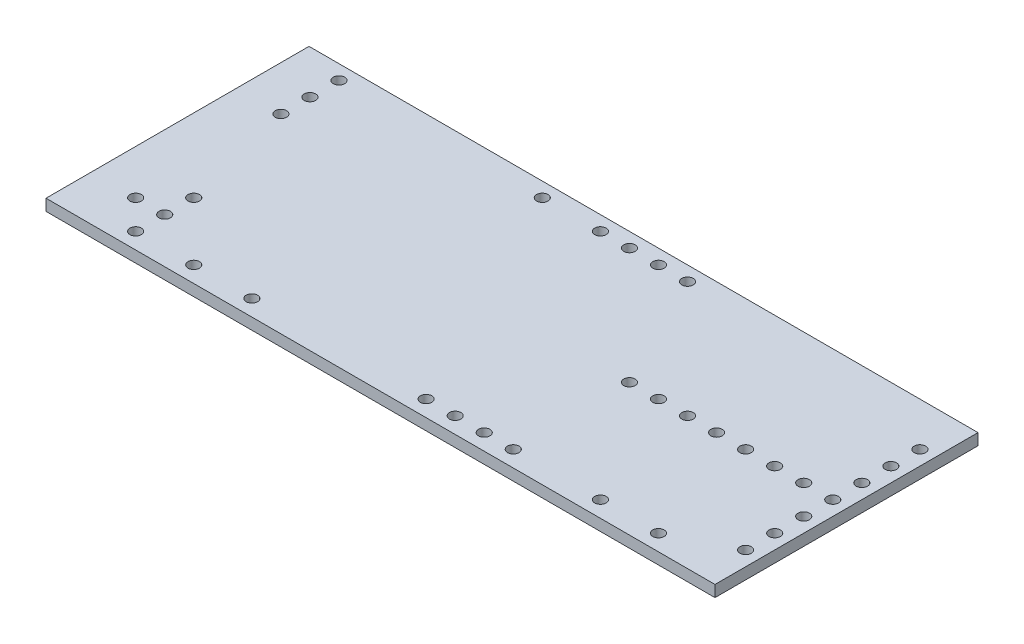
SolidWorks part; units mm, degrees
ref_plane "Front Plane" through (0, 0, 0) normal (0, 0, 1) x (1, 0, 0)
ref_plane "Top Plane" through (0, 0, 0) normal (0, 1, 0) x (1, 0, 0)
ref_plane "Right Plane" through (0, 0, 0) normal (1, 0, 0) x (0, 0, -1)
sketch "Sketch1" plane through (0, 0, 0) normal (0, 1, 0) x (1, 0, 0)
  line L1 (0, 0) -> (58.5, 0)
  line L2 (0, 0) -> (0, -23)
  line L3 (0, -23) -> (58.5, -23)
  line L4 (58.5, 0) -> (58.5, -23)
  dimension "D1" = 58.5
  dimension "D2" = 23
extrude "Boss-Extrude1" add sketch "Sketch1" along normal blind 1
sketch "Sketch2" plane through (0, 1, 0) normal (0, 1, 0) x (1, 0, 0)
  line L0 (58.5, -23) -> (58.5, 0) construction
  line L1 (58.5, 0) -> (0, 0) construction
  circle A0 centre (57.23, -3.81) radius 0.5
  circle A1 centre (57.23, -6.35) radius 0.5
  circle A2 centre (57.23, -8.89) radius 0.5
  circle A3 centre (57.23, -11.43) radius 0.5
  circle A4 centre (57.23, -13.97) radius 0.5
  circle A5 centre (57.23, -16.51) radius 0.5
  circle A6 centre (57.23, -19.05) radius 0.5
  circle A7 centre (54.69, -11.43) radius 0.5
  circle A8 centre (52.15, -11.43) radius 0.5
  circle A9 centre (49.61, -11.43) radius 0.5
  circle A10 centre (47.07, -11.43) radius 0.5
  circle A11 centre (44.53, -11.43) radius 0.5
  circle A12 centre (41.99, -11.43) radius 0.5
  circle A13 centre (39.45, -11.43) radius 0.5
  circle A14 centre (39.45, -13.97) radius 0.5 [skipped]
  circle A15 centre (39.45, -16.51) radius 0.5 [skipped]
  circle A16 centre (39.45, -19.05) radius 0.5 [skipped]
  circle A17 centre (39.45, -21.59) radius 0.5
  circle A18 centre (36.91, -21.59) radius 0.5
  circle A19 centre (34.37, -21.59) radius 0.5
  circle A20 centre (31.83, -21.59) radius 0.5
  circle A21 centre (29.29, -21.59) radius 0.5 [skipped]
  circle A22 centre (26.75, -21.59) radius 0.5 [skipped]
  circle A23 centre (24.21, -21.59) radius 0.5 [skipped]
  circle A24 centre (21.67, -21.59) radius 0.5 [skipped]
  circle A25 centre (19.13, -21.59) radius 0.5 [skipped]
  circle A26 centre (16.59, -21.59) radius 0.5
  circle A27 centre (14.05, -21.59) radius 0.5 [skipped]
  circle A28 centre (11.51, -21.59) radius 0.5
  circle A29 centre (8.97, -21.59) radius 0.5 [skipped]
  circle A30 centre (6.43, -21.59) radius 0.5
  circle A31 centre (41.99, -21.59) radius 0.5 [skipped]
  circle A32 centre (44.53, -21.59) radius 0.5 [skipped]
  circle A33 centre (47.07, -21.59) radius 0.5
  circle A34 centre (49.61, -21.59) radius 0.5 [skipped]
  circle A35 centre (52.15, -21.59) radius 0.5
  circle A36 centre (6.43, -19.05) radius 0.5
  circle A37 centre (6.43, -16.51) radius 0.5
  circle A38 centre (3.89, -19.05) radius 0.5
  circle A39 centre (3.89, -16.51) radius 0.5 [skipped]
  circle A40 centre (3.89, -13.97) radius 0.5 [skipped]
  circle A41 centre (3.89, -11.43) radius 0.5 [skipped]
  circle A42 centre (3.89, -8.89) radius 0.5 [skipped]
  circle A43 centre (3.89, -6.35) radius 0.5
  circle A44 centre (3.89, -3.81) radius 0.5
  circle A45 centre (3.89, -1.27) radius 0.5
  circle A46 centre (6.43, -1.27) radius 0.5 [skipped]
  circle A47 centre (8.97, -1.27) radius 0.5 [skipped]
  circle A48 centre (11.51, -1.27) radius 0.5 [skipped]
  circle A49 centre (14.05, -1.27) radius 0.5 [skipped]
  circle A50 centre (16.59, -1.27) radius 0.5 [skipped]
  circle A51 centre (19.13, -1.27) radius 0.5 [skipped]
  circle A52 centre (21.67, -1.27) radius 0.5
  circle A53 centre (24.21, -1.27) radius 0.5 [skipped]
  circle A54 centre (26.75, -1.27) radius 0.5
  circle A55 centre (29.29, -1.27) radius 0.5
  circle A56 centre (31.83, -1.27) radius 0.5
  circle A57 centre (34.37, -1.27) radius 0.5
  dimension "D1" = 1
  dimension "D2" = 1.27
  dimension "D3" = 3.81
  dimension "D4" = 7
  dimension "D5" = 8
  dimension "D6" = 5
  dimension "D7" = 14
  dimension "D8" = 6
  dimension "D9" = 3
  dimension "D10" = 2
  dimension "D11" = 8
  dimension "D12" = 13
extrude "Cut-Extrude1" cut sketch "Sketch2" against normal through all contours A26 | A28 | A30 | A36 | A38 | A37 | A43 | A44 | A45 | A52 | A54 | A55 | A56 | A57 | A13 | A20 | A19 | A18 | A17 | A12 | A11 | A10 | A9 | A33 | A8 | A7 | A35 | A6 | A5 | A4 | A3 | A2 | A1 | A0
